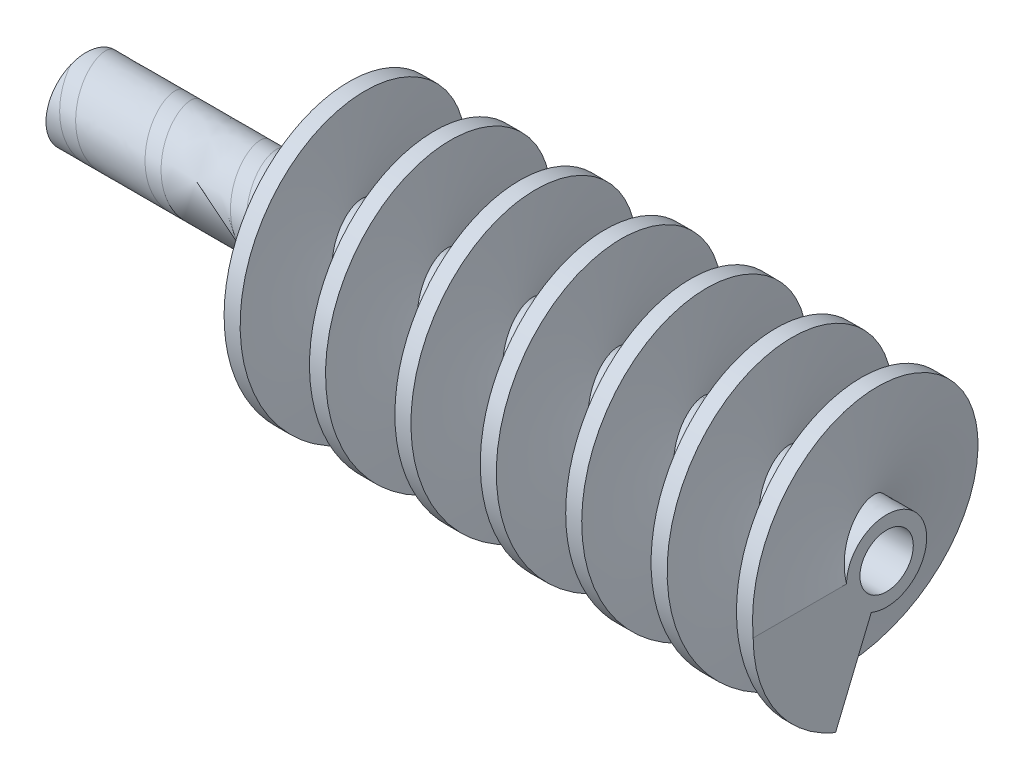
SolidWorks part; units mm, degrees
ref_plane "Alzado" through (0, 0, 0) normal (0, 0, 1) x (1, 0, 0)
ref_plane "Planta" through (0, 0, 0) normal (0, 1, 0) x (1, 0, 0)
ref_plane "Vista lateral" through (0, 0, 0) normal (1, 0, 0) x (0, 0, -1)
sketch "Croquis1" plane through (0, 0, 0) normal (1, 0, 0) x (0, 0, -1)
  circle A0 centre (0, 0) radius 25
extrude "Saliente-Extruir1" add sketch "Croquis1" along normal blind 150
sketch "Croquis2" plane through (150, 0, 0) normal (1, 0, 0) x (0, 0, -1)
  circle A0 centre (0, 0) radius 25
curve "Hélice/Espiral1" pitch 16 height 248 turns 15.5
sketch "Croquis3" plane through (0, 0, 0) normal (0, 1, 0) x (1, 0, 0)
  line L2 (150, -25) -> (163, -25)
  line L3 (163, -25) -> (163, -7.5)
  line L5 (163, -7.5) -> (150, -7.5)
  line L6 (150, -25) -> (150, -7.5)
sweep "Cortar-Barrer1" cut profiles "Croquis3" path "Hélice/Espiral1"
sketch "Croquis4" plane through (0, 0, 0) normal (0, 1, 0) x (1, 0, 0)
  line L0 (150, 0) -> (150, -5)
  line L1 (150, -7.5) -> (150, 7.5) construction
sketch "Croquis5" plane through (150, 0, 0) normal (1, 0, 0) x (0, 0, -1)
  circle A0 centre (0, 0) radius 5
extrude "Cortar-Extruir1" cut sketch "Croquis5" against normal blind 10
sketch "Croquis6" plane through (0, 0, 0) normal (-1, 0, 0) x (0, 0, 1)
  circle A0 centre (0, 0) radius 7.5
  circle A1 centre (0, 0) radius 49.6
extrude "Cortar-Extruir2" cut sketch "Croquis6" against normal blind 44
